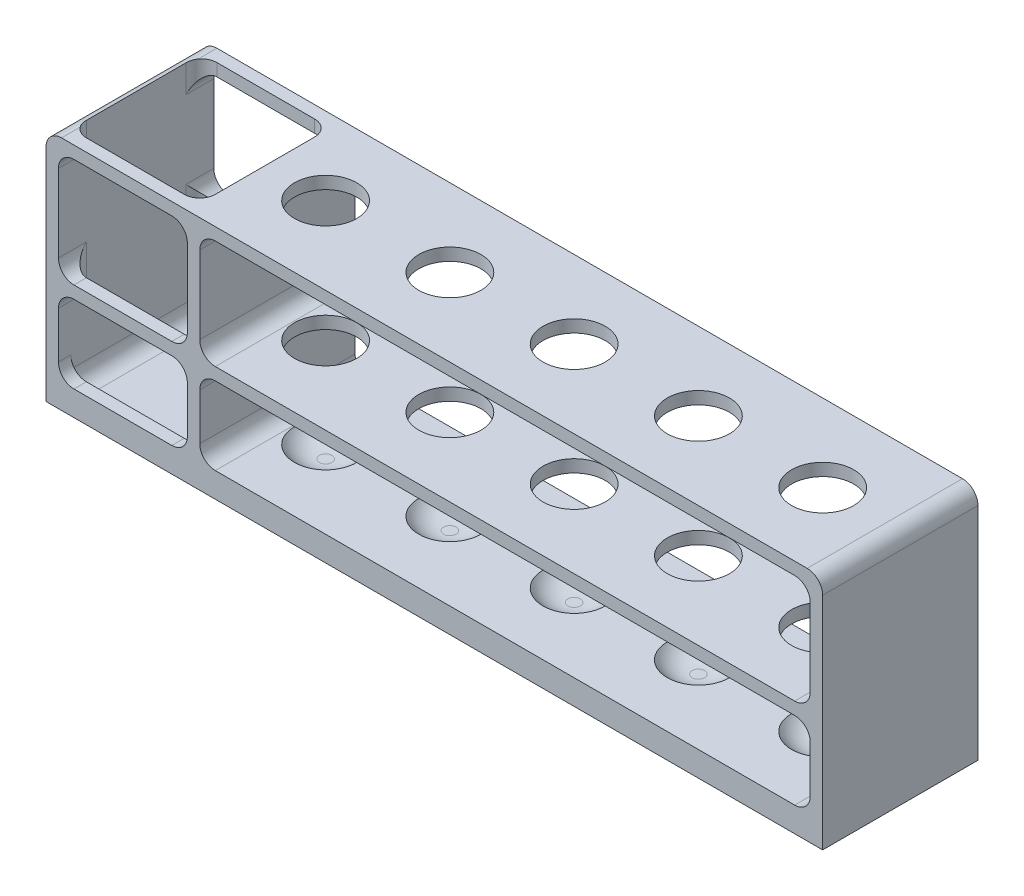
SolidWorks part; units mm, degrees
ref_plane "Front Plane" through (0, 0, 0) normal (0, 0, 1) x (1, 0, 0)
ref_plane "Top Plane" through (0, 0, 0) normal (0, 1, 0) x (1, 0, 0)
ref_plane "Right Plane" through (0, 0, 0) normal (1, 0, 0) x (0, 0, -1)
sketch "Sketch1" plane through (0, 0, 0) normal (0, 1, 0) x (1, 0, 0)
  line L1 (-39.8936, 21.0638) -> (210.1064, 21.0638)
  line L2 (-39.8936, 21.0638) -> (-39.8936, -28.9362)
  line L3 (-39.8936, -28.9362) -> (210.1064, -28.9362)
  line L4 (210.1064, 21.0638) -> (210.1064, -28.9362)
  dimension "D1" = 50
  dimension "D2" = 250
extrude "Boss-Extrude1" add sketch "Sketch1" along normal blind 8
sketch "Sketch2" plane through (0, 8, 0) normal (0, 1, 0) x (1, 0, 0)
  line L0 (-39.8936, -28.9362) -> (210.1064, -28.9362) construction
  line L1 (-39.8936, 21.0638) -> (-35.8936, 21.0638)
  line L2 (-39.8936, 21.0638) -> (-39.8936, -28.9362)
  line L3 (-39.8936, -28.9362) -> (-35.8936, -28.9362)
  line L4 (-35.8936, 21.0638) -> (-35.8936, -28.9362)
  dimension "D1" = 4
extrude "Boss-Extrude2" add sketch "Sketch2" along normal blind 25
sketch "Sketch3" plane through (0, 8, 0) normal (0, 1, 0) x (1, 0, 0)
  line L0 (-35.8936, -28.9362) -> (210.1064, -28.9362) construction
  line L1 (210.1064, 21.0638) -> (206.1064, 21.0638)
  line L2 (210.1064, 21.0638) -> (210.1064, -28.9362)
  line L3 (210.1064, -28.9362) -> (206.1064, -28.9362)
  line L4 (206.1064, 21.0638) -> (206.1064, -28.9362)
  dimension "D1" = 4
extrude "Boss-Extrude3" add sketch "Sketch3" along normal blind 25
sketch "Sketch4" plane through (0, 33, 0) normal (0, 1, 0) x (1, 0, 0)
  line L1 (-39.8936, 21.0638) -> (210.1064, 21.0638)
  line L2 (-39.8936, 21.0638) -> (-39.8936, -28.9362)
  line L3 (-39.8936, -28.9362) -> (210.1064, -28.9362)
  line L4 (210.1064, 21.0638) -> (210.1064, -28.9362)
extrude "Boss-Extrude4" add sketch "Sketch4" along normal blind 4
sketch "Sketch5" plane through (0, 37, 0) normal (0, 1, 0) x (1, 0, 0)
  line L1 (-39.8936, 21.0638) -> (-35.8936, 21.0638)
  line L2 (-39.8936, 21.0638) -> (-39.8936, -28.9362)
  line L3 (-39.8936, -28.9362) -> (-35.8936, -28.9362)
  line L4 (-35.8936, 21.0638) -> (-35.8936, -28.9362)
  line L5 (210.1064, 21.0638) -> (206.1064, 21.0638)
  line L6 (210.1064, 21.0638) -> (210.1064, -28.9362)
  line L7 (210.1064, -28.9362) -> (206.1064, -28.9362)
  line L8 (206.1064, 21.0638) -> (206.1064, -28.9362)
extrude "Boss-Extrude5" add sketch "Sketch5" along normal blind 35
sketch "Sketch6" plane through (0, 72, 0) normal (0, 1, 0) x (1, 0, 0)
  line L1 (-39.8936, 21.0638) -> (210.1064, 21.0638)
  line L2 (-39.8936, 21.0638) -> (-39.8936, -28.9362)
  line L3 (-39.8936, -28.9362) -> (210.1064, -28.9362)
  line L4 (210.1064, 21.0638) -> (210.1064, -28.9362)
extrude "Boss-Extrude6" add sketch "Sketch6" along normal blind 4
sketch "Sketch7" plane through (0, 76, 0) normal (0, 1, 0) x (1, 0, 0)
  line L0 (210.1064, 21.0638) -> (-39.8936, 21.0638) construction
  line L1 (-39.8936, 21.0638) -> (-39.8936, -28.9362) construction
  circle A2 centre (-14.8936, -3.9362) radius 10
  dimension "D1" = 25
  dimension "D2" = 25
extrude "Cut-Extrude1" cut sketch "Sketch7" against normal blind 72
pattern_linear "LPattern1" count 6 spacing 40 along (1, 0, 0) of "Cut-Extrude1"
fillet "Fillet1" radius 10 6 edges at (185.1064, 4, 13.9362) (145.1064, 4, 13.9362) (105.1064, 4, 13.9362) (65.1064, 4, 13.9362) (25.1064, 4, 13.9362) (-14.8936, 4, 13.9362)
sketch "Sketch10" plane through (0, 76, 0) normal (0, 1, 0) x (1, 0, 0)
  line L0 (-39.8936, 21.0638) -> (-39.8936, -28.9362) construction
  line L1 (-35.8936, -24.9362) -> (9.1064, -24.9362)
  line L2 (-35.8936, -24.9362) -> (-35.8936, 17.0638)
  line L3 (-35.8936, 17.0638) -> (9.1064, 17.0638)
  line L4 (9.1064, -24.9362) -> (9.1064, 17.0638)
  line L5 (210.1064, 21.0638) -> (-39.8936, 21.0638) construction
  line L6 (-39.8936, -28.9362) -> (210.1064, -28.9362) construction
  circle A0 centre (25.1064, -3.9362) radius 2 construction
  dimension "D1" = 4
  dimension "D2" = 4
  dimension "D3" = 4
  dimension "D4" = 16
extrude "Cut-Extrude3" cut sketch "Sketch10" against normal blind 72
sketch "Sketch11" plane through (0, 76, 0) normal (0, 1, 0) x (1, 0, 0)
  line L0 (210.1064, 21.0638) -> (-39.8936, 21.0638) construction
  line L1 (9.6044, 21.0638) -> (5.6044, 21.0638)
  line L2 (9.6044, 21.0638) -> (9.6044, -28.9362)
  line L3 (9.6044, -28.9362) -> (5.6044, -28.9362)
  line L4 (5.6044, 21.0638) -> (5.6044, -28.9362)
  line L5 (-39.8936, -28.9362) -> (210.1064, -28.9362) construction
  dimension "D1" = 4
extrude "Boss-Extrude8" add sketch "Sketch11" against normal blind 76
fillet "Fillet3" radius 5 1 edges at (-35.8936, 4, 3.9362)
fillet "Fillet4" radius 5 1 edges at (-35.7926, 8, -19.0638)
fillet "Fillet5" radius 5 1 edges at (-35.7926, 8, 26.9362)
fillet "Fillet6" radius 5 1 edges at (-39.8936, 76, 3.9362)
fillet "Fillet7" radius 5 2 edges at (-35.8936, 37, -19.0638) (-35.8936, 37, 26.9362)
fillet "Fillet8" radius 5 2 edges at (9.6044, 8, 3.9362) (9.6044, 37, 3.9362)
fillet "Fillet9" radius 5 6 edges at (-35.8936, 33, 26.9362) (-35.8936, 33, -19.0638) (-35.8936, 72, -19.0638) (-35.8936, 72, 26.9362) (9.6044, 72, 3.9362) (9.6044, 33, 3.9362)
fillet "Fillet10" radius 5 1 edges at (-35.8936, 71.4495, -17.0638)
fillet "Fillet11" radius 5 1 edges at (-35.8936, 35, -17.0638)
fillet "Fillet13" radius 5 3 edges at (5.6044, 37, -19.0638) (5.6044, 37, 26.9362) (5.6044, 4, 3.9362)
fillet "Fillet14" radius 5 2 edges at (5.5034, 8, -19.0638) (5.5034, 8, 26.9362)
fillet "Fillet15" radius 5 2 edges at (5.6044, 37.5, -17.0638) (5.6044, 74, -17.0638)
fillet "Fillet16" radius 5 4 edges at (5.6044, 72, 26.9362) (5.6044, 72, -16.5638) (5.6044, 33, 26.9362) (5.6044, 33, -16.5638)
fillet "Fillet17" radius 5 2 edges at (5.6044, 71.5, 24.9362) (5.6044, 35, 24.9362)
fillet "Fillet18" radius 5 2 edges at (-35.8936, 71.4495, 24.9362) (-35.8936, 35, 24.9362)
fillet "Fillet19" radius 5 2 edges at (206.1064, 8, 3.9362) (206.1064, 37, 3.9362)
fillet "Fillet20" radius 5 1 edges at (210.1064, 76, 3.9362)
fillet "Fillet21" radius 5 2 edges at (206.1064, 72, 3.9362) (206.1064, 33, 3.9362)
